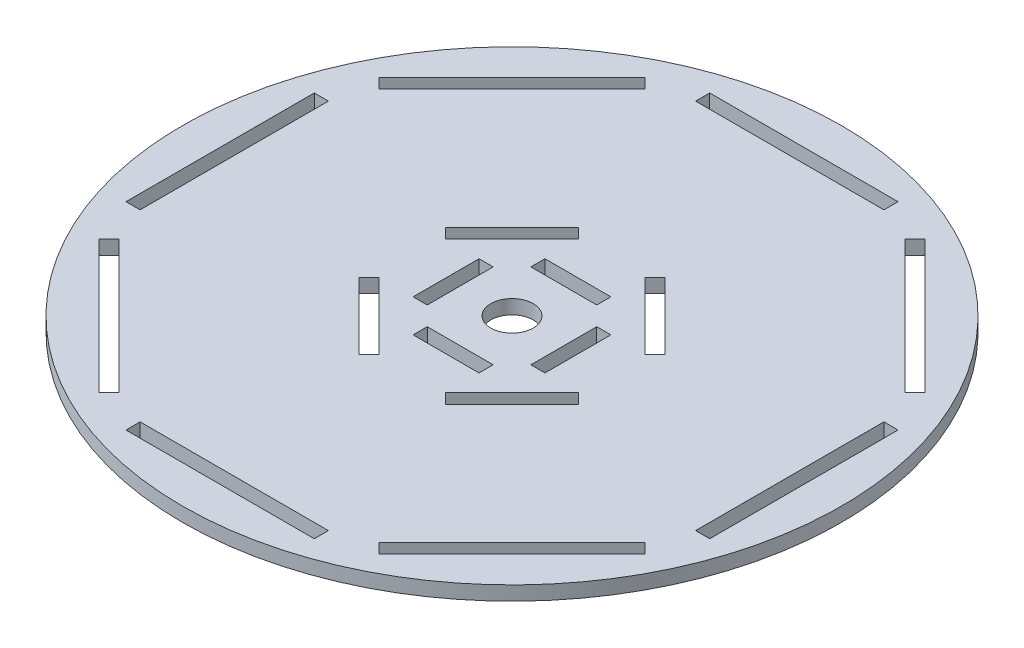
SolidWorks part; units mm, degrees
ref_plane "Alzado" through (0, 0, 0) normal (0, 0, 1) x (1, 0, 0)
ref_plane "Planta" through (0, 0, 0) normal (0, 1, 0) x (1, 0, 0)
ref_plane "Vista lateral" through (0, 0, 0) normal (1, 0, 0) x (0, 0, -1)
sketch "Croquis1" plane through (0, 0, 0) normal (0, 1, 0) x (1, 0, 0)
  line L0 (0, 11) -> (7, 11)
  line L1 (7, 11) -> (7, 14)
  line L2 (7, 14) -> (-7, 14)
  line L3 (-7, 14) -> (-7, 11)
  line L4 (-7, 11) -> (0, 11)
  line L5 (11, 0) -> (11, 7)
  line L6 (11, 7) -> (14, 7)
  line L7 (14, 7) -> (14, -7)
  line L8 (14, -7) -> (11, -7)
  line L9 (11, -7) -> (11, 0)
  line L10 (0, 0) -> (-14.1421, 14.1421) construction
  line L11 (-14.1421, 14.1421) -> (-7.0711, 21.2132)
  line L12 (-7.0711, 21.2132) -> (-9.1924, 23.3345)
  line L13 (-14, -7) -> (-11, -7)
  line L14 (-11, -7) -> (-11, 0)
  line L15 (-11, 0) -> (-11, 7)
  line L16 (-11, 7) -> (-14, 7)
  line L17 (-14, 7) -> (-14, -7)
  line L18 (7, -11) -> (7, -14)
  line L19 (0, -11) -> (7, -11)
  line L20 (7, -14) -> (-7, -14)
  line L21 (-7, -14) -> (-7, -11)
  line L22 (-7, -11) -> (0, -11)
  line L23 (-9.1924, 23.3345) -> (-23.3345, 9.1924)
  line L24 (-14.1421, 14.1421) -> (-21.2132, 7.0711)
  line L25 (-21.2132, 7.0711) -> (-23.3345, 9.1924)
  line L26 (23.3345, 9.1924) -> (9.1924, 23.3345)
  line L27 (14.1421, 14.1421) -> (21.2132, 7.0711)
  line L28 (14.1421, 14.1421) -> (7.0711, 21.2132)
  line L29 (7.0711, 21.2132) -> (9.1924, 23.3345)
  line L30 (21.2132, 7.0711) -> (23.3345, 9.1924)
  line L31 (9.1924, -23.3345) -> (23.3345, -9.1924)
  line L32 (14.1421, -14.1421) -> (7.0711, -21.2132)
  line L33 (14.1421, -14.1421) -> (21.2132, -7.0711)
  line L34 (21.2132, -7.0711) -> (23.3345, -9.1924)
  line L35 (7.0711, -21.2132) -> (9.1924, -23.3345)
  line L36 (-23.3345, -9.1924) -> (-9.1924, -23.3345)
  line L37 (-14.1421, -14.1421) -> (-21.2132, -7.0711)
  line L38 (-14.1421, -14.1421) -> (-7.0711, -21.2132)
  line L39 (-7.0711, -21.2132) -> (-9.1924, -23.3345)
  line L40 (-21.2132, -7.0711) -> (-23.3345, -9.1924)
  line L41 (0, 0) -> (0, 62) construction
  line L42 (0, 62) -> (20, 62)
  line L43 (20, 62) -> (20, 59)
  line L44 (20, 59) -> (-20, 59)
  line L45 (-20, 59) -> (-20, 62)
  line L46 (-20, 62) -> (0, 62)
  line L47 (55.8614, 27.5772) -> (27.5772, 55.8614)
  line L48 (27.5772, 55.8614) -> (29.6985, 57.9828)
  line L49 (29.6985, 57.9828) -> (43.8406, 43.8406)
  line L50 (43.8406, 43.8406) -> (57.9828, 29.6985)
  line L51 (57.9828, 29.6985) -> (55.8614, 27.5772)
  line L52 (59, -20) -> (59, 20)
  line L53 (59, 20) -> (62, 20)
  line L54 (62, 20) -> (62, 0)
  line L55 (62, 0) -> (62, -20)
  line L56 (62, -20) -> (59, -20)
  line L57 (27.5772, -55.8614) -> (55.8614, -27.5772)
  line L58 (55.8614, -27.5772) -> (57.9828, -29.6985)
  line L59 (57.9828, -29.6985) -> (43.8406, -43.8406)
  line L60 (43.8406, -43.8406) -> (29.6985, -57.9828)
  line L61 (29.6985, -57.9828) -> (27.5772, -55.8614)
  line L62 (-20, -59) -> (20, -59)
  line L63 (20, -59) -> (20, -62)
  line L64 (20, -62) -> (0, -62)
  line L65 (0, -62) -> (-20, -62)
  line L66 (-20, -62) -> (-20, -59)
  line L67 (-55.8614, -27.5772) -> (-27.5772, -55.8614)
  line L68 (-27.5772, -55.8614) -> (-29.6985, -57.9828)
  line L69 (-29.6985, -57.9828) -> (-43.8406, -43.8406)
  line L70 (-43.8406, -43.8406) -> (-57.9828, -29.6985)
  line L71 (-57.9828, -29.6985) -> (-55.8614, -27.5772)
  line L72 (-59, 20) -> (-59, -20)
  line L73 (-59, -20) -> (-62, -20)
  line L74 (-62, -20) -> (-62, 0)
  line L75 (-62, 0) -> (-62, 20)
  line L76 (-62, 20) -> (-59, 20)
  line L77 (-27.5772, 55.8614) -> (-55.8614, 27.5772)
  line L78 (-55.8614, 27.5772) -> (-57.9828, 29.6985)
  line L79 (-57.9828, 29.6985) -> (-43.8406, 43.8406)
  line L80 (-43.8406, 43.8406) -> (-29.6985, 57.9828)
  line L81 (-29.6985, 57.9828) -> (-27.5772, 55.8614)
  circle A0 centre (0, 0) radius 4.5
  circle A2 centre (0, 0) radius 70
  point P47 (0, 0)
  point P88 (0, 0)
  dimension "D1" = 9
  dimension "D2" = 14
  dimension "D3" = 140
  dimension "D4" = 7
  dimension "D5" = 3
  dimension "D6" = 14
  dimension "D7" = 20
  dimension "D8" = 3
  dimension "D9" = 10
  dimension "D10" = 3
  dimension "D11" = 20
  dimension "D12" = 10
  dimension "D14" = 62
  dimension "D15" = 20
  dimension "D16" = 3
  dimension "D17" = 40
  dimension "D13" = 4
  dimension "D18" = 8
extrude "Saliente-Extruir1" add sketch "Croquis1" along normal blind 3
